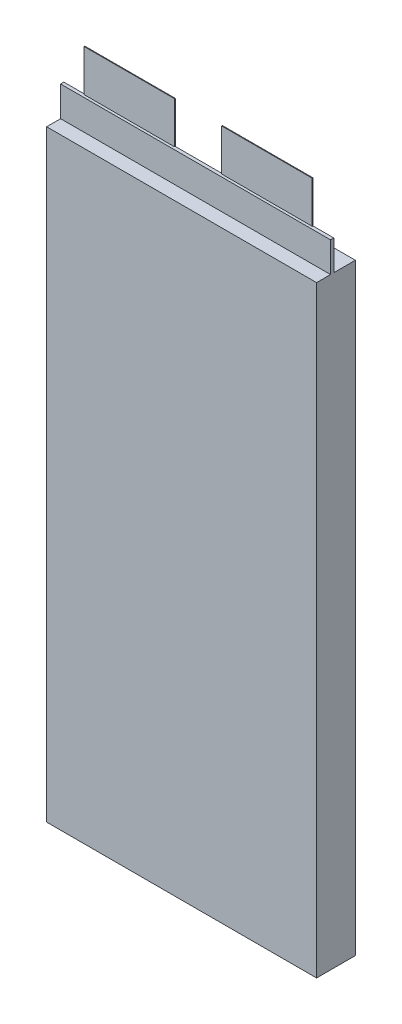
SolidWorks part; units mm, degrees
ref_plane "Front Plane" through (0, 0, 0) normal (0, 0, 1) x (1, 0, 0)
ref_plane "Top Plane" through (0, 0, 0) normal (0, 1, 0) x (1, 0, 0)
ref_plane "Right Plane" through (0, 0, 0) normal (1, 0, 0) x (0, 0, -1)
sketch "Sketch1" plane through (0, 0, 0) normal (0, 0, 1) x (1, 0, 0)
  line L0 (55, 0) -> (-55, 0) construction
  line L1 (-37.25, 0) -> (37.25, 0)
  line L2 (-37.25, 0) -> (-37.25, 166.2)
  line L3 (-37.25, 166.2) -> (37.25, 166.2)
  line L4 (37.25, 0) -> (37.25, 166.2)
  point P6 (0, 0)
  dimension "D1" = 74.5
  dimension "D2" = 166.2
extrude "Boss-Extrude1" add sketch "Sketch1" along normal blind 10.7
ref_plane "Plane1" through (0, 0, 5.95) normal (0, 0, 1) x (1, 0, 0)
sketch "Sketch2" plane through (0, 0, 5.95) normal (0, 0, 1) x (1, 0, 0)
  line L0 (37.25, 0) -> (37.25, 166.2) construction
  line L1 (-37.25, 166.2) -> (37.25, 166.2)
  line L2 (-37.25, 166.2) -> (-37.25, 174.5)
  line L3 (-37.25, 174.5) -> (37.25, 174.5)
  line L4 (37.25, 166.2) -> (37.25, 174.5)
  dimension "D1" = 8.3
extrude "Boss-Extrude2" add sketch "Sketch2" along normal blind 0.9
sketch "Sketch3" plane through (0, 0, 5.95) normal (0, 0, 1) x (1, 0, 0)
  line L0 (37.25, 174.5) -> (-37.25, 174.5) construction
  line L1 (-31.5, 174.5) -> (-6.5, 174.5)
  line L2 (-31.5, 174.5) -> (-31.5, 186)
  line L3 (-31.5, 186) -> (-6.5, 186)
  line L4 (-6.5, 174.5) -> (-6.5, 186)
  line L6 (6.5, 174.5) -> (31.5, 174.5)
  line L7 (6.5, 174.5) -> (6.5, 186)
  line L8 (6.5, 186) -> (31.5, 186)
  line L9 (31.5, 174.5) -> (31.5, 186)
  point P10 (-19, 186)
  point P11 (19, 186)
  point P12 (0, 174.5)
  dimension "D1" = 25
  dimension "D2" = 38
  dimension "D3" = 11.5
  dimension "D4" = 6.5
extrude "Boss-Extrude3" add sketch "Sketch3" along normal blind 0.2 separate body contours L1 L4 L3 L2 region at (-19, 180.25, 5.95)
extrude "Boss-Extrude4" add sketch "Sketch3<3>" along normal blind 0.2 separate body contours L6 L9 L8 L7 region at (19, 180.25, 5.95)
sketch "Sketch3<3>" plane through (0, 0, 5.95) normal (0, 0, 1) x (1, 0, 0) same geometry as "Sketch3"
